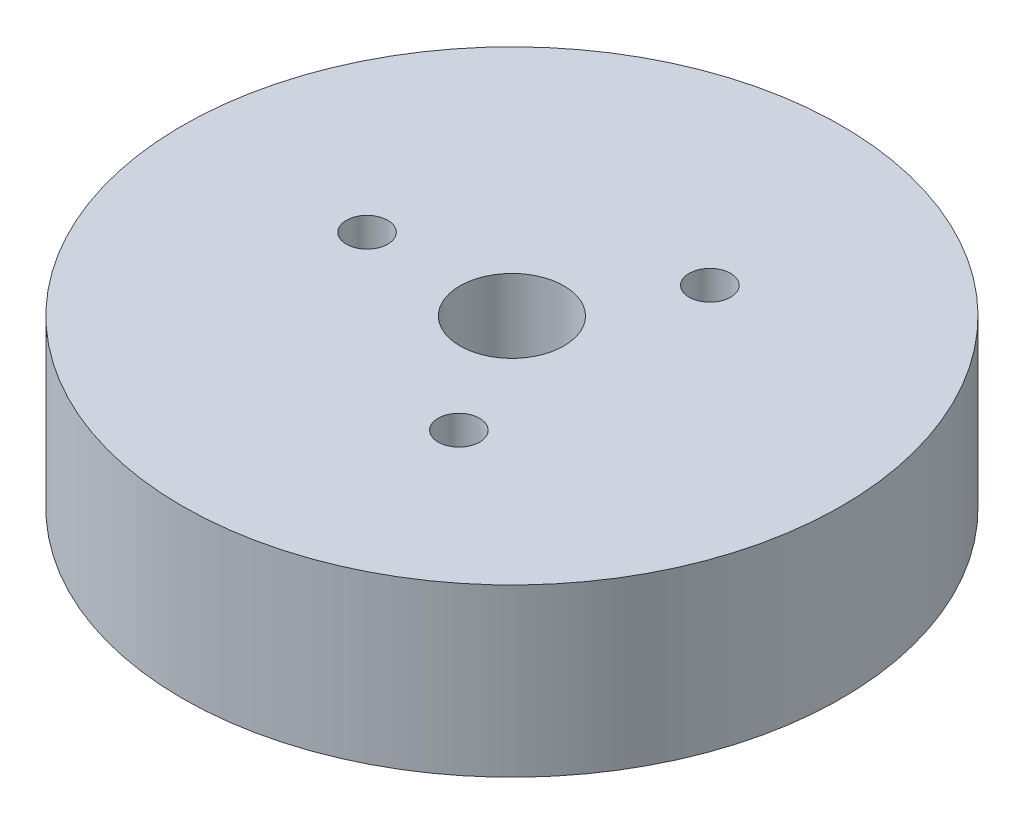
SolidWorks part; units mm, degrees
ref_plane "Front Plane" through (0, 0, 0) normal (0, 0, 1) x (1, 0, 0)
ref_plane "Top Plane" through (0, 0, 0) normal (0, 1, 0) x (1, 0, 0)
ref_plane "Right Plane" through (0, 0, 0) normal (1, 0, 0) x (0, 0, -1)
sketch "Sketch1" plane through (0, 0, 0) normal (0, 1, 0) x (1, 0, 0)
  circle A0 centre (0, 0) radius 47.5
  dimension "FLANGE_OD" = 95
extrude "Boss-Extrude1" add sketch "Sketch1" along normal blind 24
sketch "Sketch2" plane through (0, 0, 0) normal (0, 1, 0) x (1, 0, 0)
  circle A0 centre (0, 0) radius 7.5
  dimension "BORE_D" = 15
extrude "Cut-Extrude1" cut sketch "Sketch2" along normal through all
sketch "Sketch3" plane through (0, 24, 0) normal (0, 1, 0) x (1, 0, 0)
  circle A0 centre (0, 0) radius 20.8842 construction
  circle A1 centre (-20.8842, 0) radius 2.9865
  dimension "BOLT_D" = 5.9729
  dimension "BOLT_PCD" = 41.7684
extrude "Cut-Extrude2" cut sketch "Sketch3" against normal blind 19.3289
pattern_circular "CirPattern1" count 3 over 360 about axis through (0, 0, 0) along (0, 1, 0) of "Cut-Extrude2"
